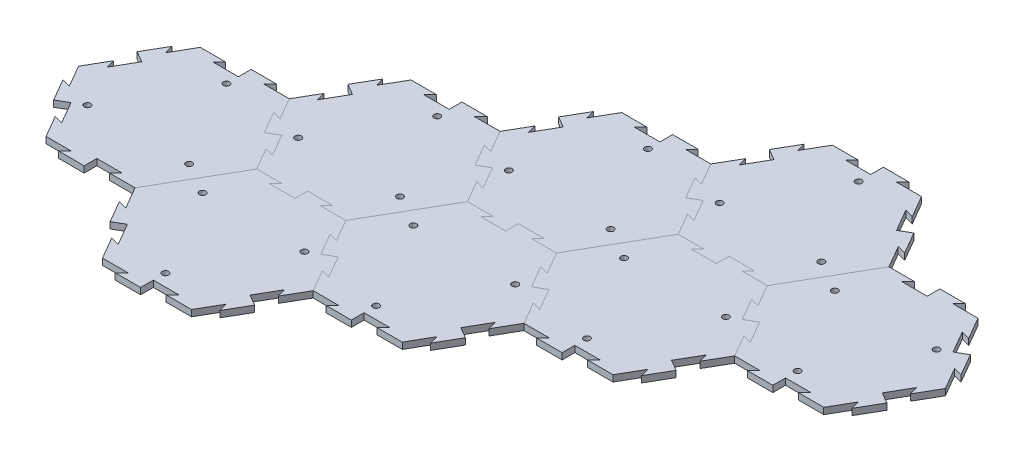
SolidWorks part; units mm, degrees
material "Cedar"
ref_plane "Front Plane" through (0, 0, 0) normal (0, 0, 1) x (1, 0, 0)
ref_plane "Top Plane" through (0, 0, 0) normal (0, 1, 0) x (1, 0, 0)
ref_plane "Right Plane" through (0, 0, 0) normal (1, 0, 0) x (0, 0, -1)
sketch "Sketch1" plane through (0, 0, 0) normal (0, 1, 0) x (1, 0, 0)
  line L0 (0, 0) -> (88.9, 0) construction
  line L1 (88.9, 0) -> (44.45, 76.9897)
  line L2 (44.45, 76.9897) -> (-44.45, 76.9897)
  line L3 (-44.45, 76.9897) -> (-88.9, 0)
  line L4 (-88.9, 0) -> (-44.45, -76.9897)
  line L5 (-44.45, -76.9897) -> (44.45, -76.9897)
  line L6 (44.45, -76.9897) -> (88.9, 0)
  circle A0 centre (0, 0) radius 76.9897 construction
  dimension "D1" = 88.9
extrude "Boss-Extrude1" add sketch "Sketch1" against normal blind 6.35
sketch "Sketch2" plane through (0, 0, 0) normal (0, 1, 0) x (1, 0, 0)
  point P1 (0, 0)
ref_axis "Axis1" through (0, 0, 0) along (0, 1, 0)
sketch "Sketch9" plane through (0, 0, 0) normal (0, 1, 0) x (1, 0, 0)
  line L1 (50.8, -29.3294) -> (0, 58.6588) construction
  line L2 (0, 58.6588) -> (-50.8, -29.3294) construction
  line L3 (-50.8, -29.3294) -> (50.8, -29.3294) construction
  circle A0 centre (0, 0) radius 29.3294 construction
  circle A1 centre (-50.8, -29.3294) radius 3.175
  dimension "D2" = 6.35
  dimension "D1" = 101.6
extrude "Cut-Extrude3" cut sketch "Sketch9" against normal through all
pattern_circular "CirPattern6" count 3 over 360 about axis through (0, 0, 0) along (0, 1, 0) of "Cut-Extrude3"
mirror "Mirror3" about plane through (44.45, -6.35, 76.9897) normal (0.866, 0, 0.5) of bodies 121 125
sketch "Sketch10" plane through (0, 0, 0) normal (0, 1, 0) x (1, 0, 0)
  line L0 (44.45, 76.9897) -> (57.15, 54.9926) construction
  line L1 (57.15, 54.9926) -> (48.4757, 57.3169)
  line L2 (48.4757, 57.3169) -> (61.1757, 35.3198)
  line L3 (61.1757, 35.3198) -> (66.675, 38.4948)
  line L4 (57.15, 54.9926) -> (66.675, 38.4948)
  line L5 (88.9, 0) -> (44.45, 76.9897) construction
  dimension "D1" = 45
  dimension "D2" = 6.35
extrude "Cut-Extrude4" cut sketch "Sketch10" against normal through all
sketch "Sketch11" plane through (0, 0, 0) normal (0, 1, 0) x (1, 0, 0)
  line L0 (66.675, 38.4948) -> (88.9, 0) construction
  line L1 (66.675, 38.4948) -> (72.1743, 41.6698)
  line L2 (72.1743, 41.6698) -> (84.8743, 19.6728)
  line L3 (84.8743, 19.6728) -> (76.2, 21.997)
  line L4 (76.2, 21.997) -> (66.675, 38.4948)
  line L5 (76.2, 21.997) -> (88.9, 0) construction
  line L6 (76.2, 21.997) -> (88.9, 0) construction
  line L7 (88.9, 0) -> (66.675, 38.4948) construction
  line L8 (44.45, -76.9897) -> (88.9, 0) construction
  dimension "D1" = 45
  dimension "D2" = 6.35
extrude "Boss-Extrude4" add sketch "Sketch11" against normal blind 6.35
pattern_circular "CirPattern7" count 6 over 360 about axis through (0, 0, 0) along (0, 1, 0) skipping 5 of "Cut-Extrude4", "Boss-Extrude4"
sketch "Sketch12" plane through (0, 0, 0) normal (0, 1, 0) x (1, 0, 0)
  line L0 (177.8, 0) -> (88.9, -153.9793) construction
  point P4 (133.35, -76.9897)
ref_axis "Axis2" through (133.35, 0, 76.9897) along (0, 1, 0)
sketch "Sketch13" plane through (0, 0, 0) normal (0, 1, 0) x (1, 0, 0)
  line L0 (177.8, 0) -> (190.5, -21.997) construction
  line L1 (190.5, -21.997) -> (181.8257, -19.6728)
  line L2 (181.8257, -19.6728) -> (194.5257, -41.6698)
  line L3 (194.5257, -41.6698) -> (200.025, -38.4948)
  line L4 (190.5, -21.997) -> (200.025, -38.4948)
  line L5 (177.8, 0) -> (222.25, -76.9897) construction
  dimension "D1" = 45
  dimension "D2" = 6.35
extrude "Cut-Extrude5" cut sketch "Sketch13" against normal through all
sketch "Sketch14" plane through (0, 0, 0) normal (0, 1, 0) x (1, 0, 0)
  line L0 (200.025, -38.4948) -> (222.25, -76.9897) construction
  line L1 (200.025, -38.4948) -> (205.5243, -35.3198)
  line L2 (205.5243, -35.3198) -> (218.2243, -57.3169)
  line L3 (218.2243, -57.3169) -> (209.55, -54.9926)
  line L4 (209.55, -54.9926) -> (200.025, -38.4948)
  line L5 (209.55, -54.9926) -> (222.25, -76.9897) construction
  line L6 (209.55, -54.9926) -> (222.25, -76.9897) construction
  dimension "D1" = 45
  dimension "D2" = 6.35
extrude "Boss-Extrude5" add sketch "Sketch14" against normal blind 6.35
pattern_circular "CirPattern8" count 6 over 360 about axis through (133.35, 0, 76.9897) along (0, 1, 0) skipping 2 of "Cut-Extrude5", "Boss-Extrude5"
pattern_linear "LPattern1" count 4 spacing 153.9793 along (0.866, 0, -0.5) of bodies 125 129
